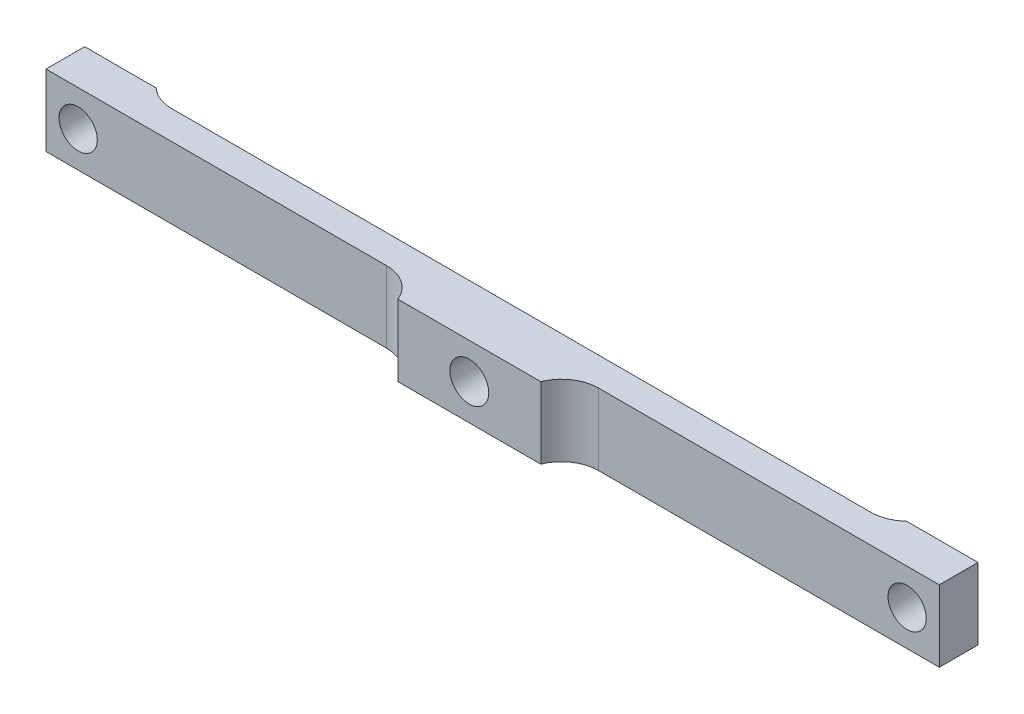
SolidWorks part; units mm, degrees
ref_plane "Front Plane" through (0, 0, 0) normal (0, 0, 1) x (1, 0, 0)
ref_plane "Top Plane" through (0, 0, 0) normal (0, 1, 0) x (1, 0, 0)
ref_plane "Right Plane" through (0, 0, 0) normal (1, 0, 0) x (0, 0, -1)
sketch "Sketch1" plane through (0, 0, 0) normal (0, 0, 1) x (1, 0, 0)
  line L1 (-39.6875, -3.175) -> (39.6875, -3.175)
  line L2 (-39.6875, -3.175) -> (-39.6875, 3.175)
  line L3 (-39.6875, 3.175) -> (39.6875, 3.175)
  line L4 (39.6875, -3.175) -> (39.6875, 3.175)
  line L5 (-39.6875, -3.175) -> (39.6875, 3.175) construction
  line L6 (-39.6875, 3.175) -> (39.6875, -3.175) construction
  point P0 (0, 0)
  dimension "D1" = 6.35
  dimension "D2" = 79.375
extrude "Boss-Extrude1" add sketch "Sketch1" along normal blind 5.5118
sketch "Sketch10" plane through (0, 0, 0) normal (0, 0, -1) x (-1, 0, 0)
  line L0 (39.6875, -3.175) -> (-39.6875, -3.175) construction
  line L1 (33.3375, 3.175) -> (-33.3375, 3.175)
  line L2 (33.3375, 3.175) -> (33.3375, -3.175)
  line L3 (33.3375, -3.175) -> (-33.3375, -3.175)
  line L4 (-33.3375, 3.175) -> (-33.3375, -3.175)
  line L5 (33.3375, 3.175) -> (-33.3375, -3.175) construction
  line L6 (33.3375, -3.175) -> (-33.3375, 3.175) construction
  line L7 (-39.6875, -3.175) -> (-39.6875, 3.175) construction
  point P0 (0, 0)
  dimension "D1" = 6.35
extrude "Cut-Extrude2" cut sketch "Sketch10" against normal blind 0.8992
sketch "Sketch2" plane through (0, 0, 5.5118) normal (0, 0, 1) x (1, 0, 0)
  line L0 (-39.6875, -3.175) -> (39.6875, -3.175) construction
  line L1 (39.6875, 3.175) -> (6.35, 3.175)
  line L2 (39.6875, 3.175) -> (39.6875, -3.175)
  line L3 (39.6875, -3.175) -> (6.35, -3.175)
  line L4 (6.35, 3.175) -> (6.35, -3.175)
  dimension "D1" = 6.35
extrude "Cut-Extrude1" cut sketch "Sketch2" against normal offset from surface (2.0726 mm away) 2.54 up to face at (0, 0, 0.8992)
sketch "Sketch3" plane through (0, 0, 3.4392) normal (0, 0, 1) x (1, 0, 0)
  line L0 (0, 0) -> (36.83, 0) construction
  line L1 (36.83, 0) -> (40.005, 0) construction
  dimension "D1" = 36.83
  dimension "D2" = 40.005
hole_wizard "M3 Clearance Hole1" positions "Sketch5" profile "Sketch6" hole size "M3" standard "Ansi Metric" end condition through all
sketch "Sketch5" plane through (0, 0, 3.4392) normal (0, 0, 1) x (1, 0, 0)
  point P7 (36.83, 0)
sketch "Sketch6" plane through (36.83, 0, 3.4392) normal (1, 0, 0) x (0, -1, 0)
  line L0 (0, 0) -> (0, 3.4392)
  line L1 (0, 3.4392) -> (1.7, 3.4392)
  line L2 (1.7, 3.4392) -> (1.7, 0)
  line L5 (1.7, 0) -> (0, 0)
  line L11 (0, -6.35) -> (0, 107.95) construction
  dimension "Thru Hole Dia." = 3.4
  dimension "Thru Hole Depth" = 3.4392
mirror "Mirror2" about plane through (0, 0, 0) normal (1, 0, 0) of "M3 Clearance Hole1", "Cut-Extrude1"
hole_wizard "#8-32 Tapped Hole1" positions "Sketch8" profile "Sketch9" tap size "#8-32" standard "Ansi Inch" end condition through all
sketch "Sketch8" plane through (0, 0, 5.5118) normal (0, 0, 1) x (1, 0, 0)
  point P1 (0, 0)
sketch "Sketch9" plane through (0, 0, 5.5118) normal (1, 0, 0) x (0, -1, 0)
  line L0 (0, 0) -> (0, 5.5118)
  line L1 (0, 5.5118) -> (1.7272, 5.5118)
  line L2 (1.7272, 5.5118) -> (1.7272, 0)
  line L5 (1.7272, 0) -> (0, 0)
  line L11 (0, -6.35) -> (0, 107.95) construction
  dimension "Thru Tap Drill Dia." = 3.4544
  dimension "Thru Tap Drill Depth" = 5.5118
cosmetic thread "Hole Thread1" parameters "D2"=4.1656
fillet "Fillet1" radius 3.302 4 edges at (33.3375, 0, 0.8992) (6.35, 0, 3.4392) (-6.35, 0, 3.4392) (-33.3375, 0, 0.8992)
sketch "Sketch11" plane through (-39.6875, 0, 0) normal (-1, 0, 0) x (0, 0, 1)
  line L0 (0, 3.175) -> (0, 28.575) construction
  dimension "D1" = 25.4
